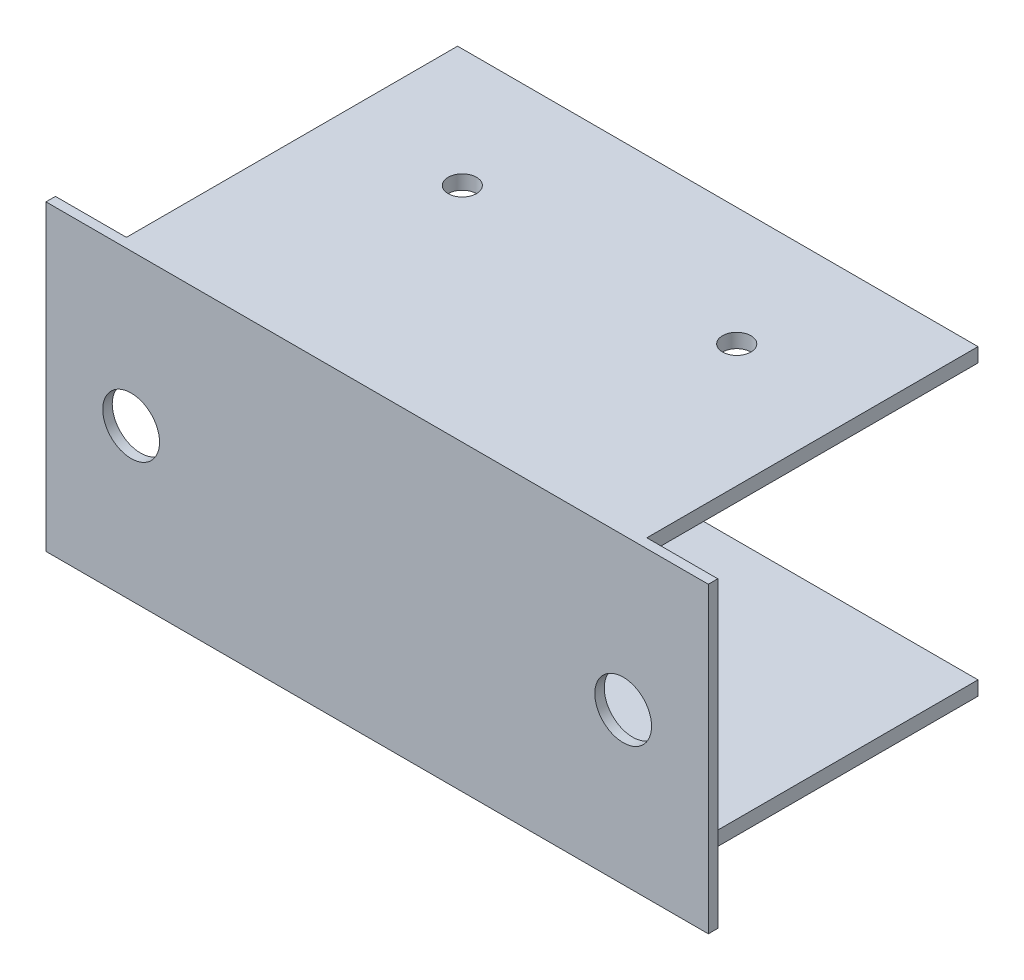
SolidWorks part; units mm, degrees
ref_plane "前视基准面" through (0, 0, 0) normal (0, 0, 1) x (1, 0, 0)
ref_plane "上视基准面" through (0, 0, 0) normal (0, 1, 0) x (1, 0, 0)
ref_plane "右视基准面" through (0, 0, 0) normal (1, 0, 0) x (0, 0, -1)
sketch "草图1" plane through (0, 0, 0) normal (0, 0, 1) x (1, 0, 0)
  line L1 (-35, 16) -> (35, 16)
  line L2 (-35, 16) -> (-35, -16)
  line L3 (-35, -16) -> (35, -16)
  line L4 (35, 16) -> (35, -16)
  line L5 (-35, 16) -> (35, -16) construction
  line L6 (-35, -16) -> (35, 16) construction
  point P0 (0, 0)
  dimension "D1" = 70
  dimension "D2" = 32
extrude "凸台-拉伸1" add sketch "草图1" along normal blind 1 contours L2 L3 L4 L1
sketch "草图2" plane through (0, 0, 1) normal (0, 0, 1) x (1, 0, 0)
  line L0 (-26, 0) -> (26, 0) construction
  circle A0 centre (-26, 0) radius 3
  circle A1 centre (26, 0) radius 3
  point P2 (0, 0)
  dimension "D2" = 6
  dimension "D3" = 6
  dimension "D1" = 52
extrude "切除-拉伸1" cut sketch "草图2" against normal blind 10
sketch "草图4" plane through (0, 16, 0) normal (0, 1, 0) x (1, 0, 0)
  line L0 (-35, -1) -> (35, -1) construction
  line L1 (-27.5, 35) -> (27.5, 35)
  line L2 (-27.5, 35) -> (-27.5, -1)
  line L3 (-27.5, -1) -> (27.5, -1)
  line L4 (27.5, 35) -> (27.5, -1)
  line L5 (-27.5, 35) -> (27.5, -1) construction
  line L6 (-27.5, -1) -> (27.5, 35) construction
  point P0 (0, 17)
  dimension "D1" = 36
  dimension "D2" = 55
extrude "凸台-拉伸2" add sketch "草图4" against normal blind 1.5
sketch "草图5" plane through (0, 16, 0) normal (0, 1, 0) x (1, 0, 0)
  line L0 (-14.5, 22.5) -> (14.5, 22.5) construction
  line L1 (27.5, 35) -> (-27.5, 35) construction
  circle A0 centre (-14.5, 22.5) radius 1.5
  circle A1 centre (14.5, 22.5) radius 1.5
  point P2 (0, 22.5)
  dimension "D3" = 3
  dimension "D4" = 3
  dimension "D1" = 12.5
  dimension "D2" = 29
extrude "切除-拉伸2" cut sketch "草图5" against normal through all
mirror "镜向1" about plane through (0, 0, 0) normal (0, 1, 0) of "凸台-拉伸2"
